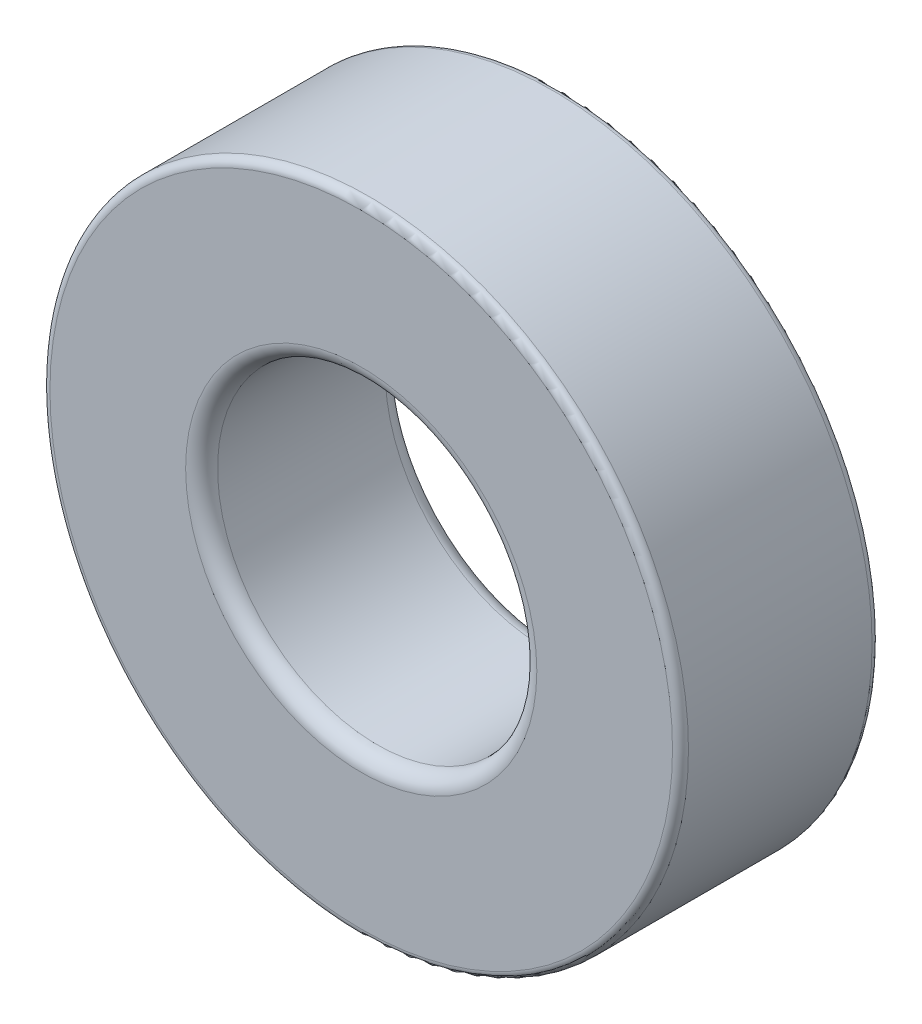
SolidWorks part; units mm, degrees
material "Alloy Steel"
ref_plane "Front Plane" through (0, 0, 0) normal (0, 0, 1) x (1, 0, 0)
ref_plane "Top Plane" through (0, 0, 0) normal (0, 1, 0) x (1, 0, 0)
ref_plane "Right Plane" through (0, 0, 0) normal (1, 0, 0) x (0, 0, -1)
sketch "Sketch1" plane through (0, 0, 0) normal (0, 0, 1) x (1, 0, 0)
  circle A0 centre (0, 0) radius 4
  circle A1 centre (0, 0) radius 8
  dimension "D1" = 16
  dimension "D2" = 8
extrude "Bearing Boss-Extrude1" add sketch "Sketch1" along normal blind 2.5 and the other way blind 2.5
fillet "Fillet6" radius 0.2 2 edges at (8, 0, 2.5) (8, 0, -2.5)
fillet "Fillet7" radius 0.4 2 edges at (4, 0, -2.5) (4, 0, 2.5)
